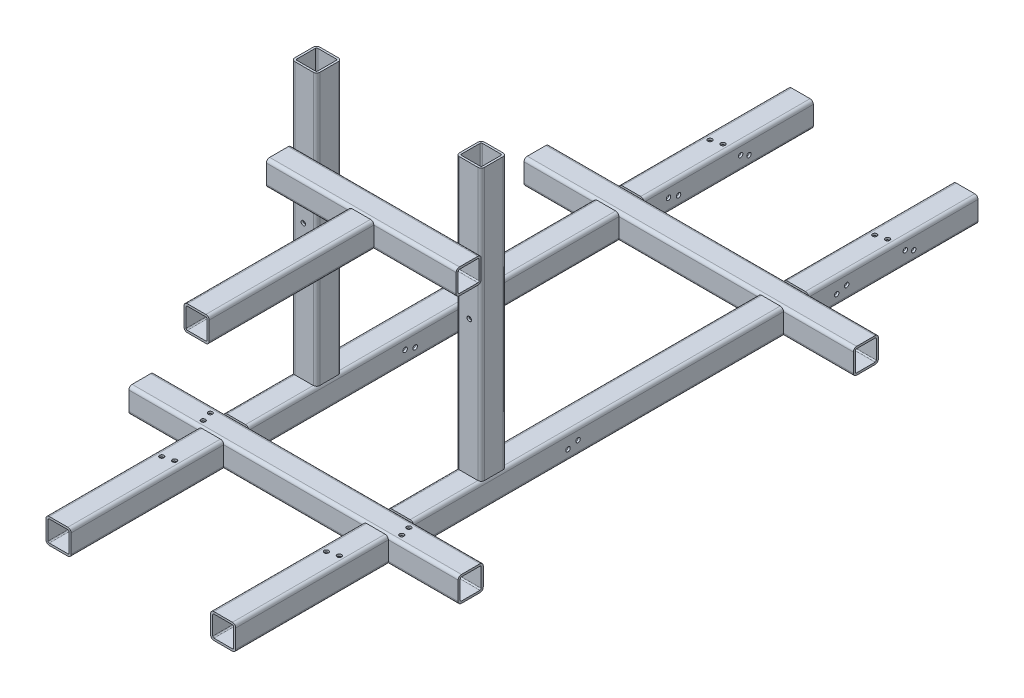
SolidWorks part; units mm, degrees
material "Alumina"
ref_plane "Front Plane" through (0, 0, 0) normal (0, 0, 1) x (1, 0, 0)
ref_plane "Top Plane" through (0, 0, 0) normal (0, 1, 0) x (1, 0, 0)
ref_plane "Right Plane" through (0, 0, 0) normal (1, 0, 0) x (0, 0, -1)
ref_plane "Bottom Face" through (0, 0, 0) normal (0, 1, 0) x (1, 0, 0)
ref_plane "Top Face" through (0, 38.1, 0) normal (0, 1, 0) x (1, 0, 0)
ref_plane "Mid Plane" through (0, 19.05, 0) normal (0, 1, 0) x (1, 0, 0)
ref_plane "Front Face" through (0, 0, 500) normal (0, 0, 1) x (1, 0, 0)
ref_plane "Back Face" through (0, 0, -500) normal (0, 0, 1) x (1, 0, 0)
ref_plane "Left Face" through (250, 0, 0) normal (1, 0, 0) x (0, 0, -1)
ref_plane "Right Face" through (-250, 0, 0) normal (1, 0, 0) x (0, 0, -1)
ref_plane "Divider Plane" through (0, 0, 140) normal (0, 0, 1) x (1, 0, 0)
ref_plane "Max Height Plane" through (0, 450, 0) normal (0, 1, 0) x (1, 0, 0)
ref_plane "Electronics Box Plane" through (0, 338.1, 0) normal (0, 1, 0) x (1, 0, 0)
sketch "Sketch2" plane through (250, 0, 0) normal (1, 0, 0) x (0, 0, -1)
  line L0 (330, 38.1) -> (-330, 38.1) construction
  line L5 (330, 0) -> (-330, 0) construction
  line L6 (0, 220) -> (0, -220) construction
  line L7 (-314.05, 38.1) -> (-285.95, 38.1)
  line L8 (-280.95, 33.1) -> (-280.95, 5)
  line L9 (-315.875, 33.1) -> (-315.875, 5)
  line L10 (-314.05, 3.175) -> (-285.95, 3.175)
  line L11 (-285.95, 0) -> (-314.05, 0)
  line L12 (-319.05, 5) -> (-319.05, 33.1)
  line L13 (-300, 38.1) -> (-300, 0) construction
  line L14 (-319.05, 19.05) -> (-280.95, 19.05) construction
  line L15 (-284.125, 5) -> (-284.125, 33.1)
  line L16 (-285.95, 34.925) -> (-314.05, 34.925)
  line L17 (-300, 34.925) -> (-300, 3.175) construction
  line L18 (-315.875, 19.05) -> (-284.125, 19.05) construction
  arc A0 (-285.95, 38.1) -> (-280.95, 33.1) centre (-285.95, 33.1) cw
  arc A1 (-280.95, 5) -> (-285.95, 0) centre (-285.95, 5) cw
  arc A2 (-314.05, 0) -> (-319.05, 5) centre (-314.05, 5) cw
  arc A3 (-319.05, 33.1) -> (-314.05, 38.1) centre (-314.05, 33.1) cw
  arc A4 (-315.875, 5) -> (-314.05, 3.175) centre (-314.05, 5) ccw
  arc A5 (-285.95, 3.175) -> (-284.125, 5) centre (-285.95, 5) ccw
  arc A6 (-284.125, 33.1) -> (-285.95, 34.925) centre (-285.95, 33.1) ccw
  arc A7 (-314.05, 34.925) -> (-315.875, 33.1) centre (-314.05, 33.1) ccw
  point P20 (-300, 19.05)
  point P39 (-300, 19.05)
  dimension "D1" = 5
  dimension "D2" = 300
  dimension "D3" = 3.175
extrude "Front Cross-Car Member" add sketch "Sketch2" against normal up to surface (500 mm away) up to plane "Right Face"
sketch "Sketch5" plane through (250, 0, 0) normal (1, 0, 0) x (0, 0, -1)
  line L0 (285.95, 38.1) -> (314.05, 38.1)
  line L1 (319.05, 33.1) -> (319.05, 5)
  line L2 (314.05, 0) -> (285.95, 0)
  line L3 (280.95, 5) -> (280.95, 33.1)
  line L4 (300, 38.1) -> (300, 0) construction
  line L5 (280.95, 19.05) -> (319.05, 19.05) construction
  line L6 (285.95, 34.925) -> (314.05, 34.925)
  line L7 (315.875, 33.1) -> (315.875, 5)
  line L8 (314.05, 3.175) -> (285.95, 3.175)
  line L9 (284.125, 5) -> (284.125, 33.1)
  line L10 (300, 34.925) -> (300, 3.175) construction
  line L11 (284.125, 19.05) -> (315.875, 19.05) construction
  line L12 (330, 0) -> (-330, 0) construction
  line L14 (330, 38.1) -> (-330, 38.1) construction
  line L15 (0, 220) -> (0, -220) construction
  arc A0 (314.05, 38.1) -> (319.05, 33.1) centre (314.05, 33.1) cw
  arc A1 (319.05, 5) -> (314.05, 0) centre (314.05, 5) cw
  arc A2 (285.95, 0) -> (280.95, 5) centre (285.95, 5) cw
  arc A3 (280.95, 33.1) -> (285.95, 38.1) centre (285.95, 33.1) cw
  arc A4 (314.05, 34.925) -> (315.875, 33.1) centre (314.05, 33.1) cw
  arc A5 (315.875, 5) -> (314.05, 3.175) centre (314.05, 5) cw
  arc A6 (285.95, 3.175) -> (284.125, 5) centre (285.95, 5) cw
  arc A7 (284.125, 33.1) -> (285.95, 34.925) centre (285.95, 33.1) cw
  point P32 (300, 19.05)
  point P33 (300, 19.05)
  dimension "D2" = 5
  dimension "D1" = 3.175
  dimension "D3" = 300
extrude "Back Cross-Car Member" add sketch "Sketch5" against normal up to surface (500 mm away) separate body up to plane "Right Face"
sketch "Sketch6" plane through (0, 0, -500) normal (0, 0, 1) x (1, 0, 0)
  line L0 (110.95, 38.1) -> (139.05, 38.1)
  line L1 (144.05, 33.1) -> (144.05, 5)
  line L2 (109.125, 33.1) -> (109.125, 5)
  line L3 (110.95, 3.175) -> (139.05, 3.175)
  line L4 (139.05, 0) -> (110.95, 0)
  line L5 (105.95, 5) -> (105.95, 33.1)
  line L6 (125, 38.1) -> (125, 0) construction
  line L7 (105.95, 19.05) -> (144.05, 19.05) construction
  line L8 (140.875, 5) -> (140.875, 33.1)
  line L9 (139.05, 34.925) -> (110.95, 34.925)
  line L10 (125, 34.925) -> (125, 3.175) construction
  line L11 (109.125, 19.05) -> (140.875, 19.05) construction
  line L12 (330, 38.1) -> (-330, 38.1) construction
  line L13 (330, 0) -> (-330, 0) construction
  line L14 (0, -220) -> (0, 220) construction
  arc A0 (139.05, 38.1) -> (144.05, 33.1) centre (139.05, 33.1) cw
  arc A1 (144.05, 5) -> (139.05, 0) centre (139.05, 5) cw
  arc A2 (110.95, 0) -> (105.95, 5) centre (110.95, 5) cw
  arc A3 (105.95, 33.1) -> (110.95, 38.1) centre (110.95, 33.1) cw
  arc A4 (109.125, 5) -> (110.95, 3.175) centre (110.95, 5) ccw
  arc A5 (139.05, 3.175) -> (140.875, 5) centre (139.05, 5) ccw
  arc A6 (140.875, 33.1) -> (139.05, 34.925) centre (139.05, 33.1) ccw
  arc A7 (110.95, 34.925) -> (109.125, 33.1) centre (110.95, 33.1) ccw
  point P16 (125, 19.05)
  point P33 (125, 19.05)
  dimension "D1" = 5
  dimension "D2" = 3.175
  dimension "D3" = 125
extrude "Back Left Along-Car Member" add sketch "Sketch6" along normal blind 180.95 and the other way blind 76.2
extrude "Middle Left Along-Car Member" add sketch "Sketch6<2>" along normal blind 561.9 from offset 219.05
sketch "Sketch6<2>" plane through (0, 0, -500) normal (0, 0, 1) x (1, 0, 0) same geometry as "Sketch6"
extrude "Front Left Along-Car Member" add sketch "Sketch6<3>" along normal blind 231.75 from offset 819.05
sketch "Sketch6<3>" plane through (0, 0, -500) normal (0, 0, 1) x (1, 0, 0) same geometry as "Sketch6"
sketch "Sketch7" plane through (0, 0, -500) normal (0, 0, 1) x (1, 0, 0)
  line L0 (-139.05, 38.1) -> (-110.95, 38.1)
  line L1 (-105.95, 33.1) -> (-105.95, 5)
  line L2 (-140.875, 33.1) -> (-140.875, 5)
  line L3 (-139.05, 3.175) -> (-110.95, 3.175)
  line L4 (-110.95, 0) -> (-139.05, 0)
  line L5 (-144.05, 5) -> (-144.05, 33.1)
  line L6 (-125, 38.1) -> (-125, 0) construction
  line L7 (-144.05, 19.05) -> (-105.95, 19.05) construction
  line L8 (-109.125, 5) -> (-109.125, 33.1)
  line L9 (-110.95, 34.925) -> (-139.05, 34.925)
  line L10 (-125, 34.925) -> (-125, 3.175) construction
  line L11 (-140.875, 19.05) -> (-109.125, 19.05) construction
  line L12 (330, 38.1) -> (-330, 38.1) construction
  line L13 (330, 0) -> (-330, 0) construction
  line L14 (0, -220) -> (0, 220) construction
  arc A0 (-110.95, 38.1) -> (-105.95, 33.1) centre (-110.95, 33.1) cw
  arc A1 (-105.95, 5) -> (-110.95, 0) centre (-110.95, 5) cw
  arc A2 (-139.05, 0) -> (-144.05, 5) centre (-139.05, 5) cw
  arc A3 (-144.05, 33.1) -> (-139.05, 38.1) centre (-139.05, 33.1) cw
  arc A4 (-140.875, 5) -> (-139.05, 3.175) centre (-139.05, 5) ccw
  arc A5 (-110.95, 3.175) -> (-109.125, 5) centre (-110.95, 5) ccw
  arc A6 (-109.125, 33.1) -> (-110.95, 34.925) centre (-110.95, 33.1) ccw
  arc A7 (-139.05, 34.925) -> (-140.875, 33.1) centre (-139.05, 33.1) ccw
  point P16 (-125, 19.05)
  point P33 (-125, 19.05)
  dimension "D1" = 5
  dimension "D2" = 3.175
  dimension "D3" = 125
extrude "Back Right Along-Car Member" add sketch "Sketch7" along normal blind 180.95 and the other way blind 76.2
extrude "Middle Right Along-Car Member" add sketch "Sketch7<2>" along normal blind 561.9 from offset 219.05
sketch "Sketch7<2>" plane through (0, 0, -500) normal (0, 0, 1) x (1, 0, 0) same geometry as "Sketch7"
extrude "Front Right Along-Car Member" add sketch "Sketch7<3>" along normal blind 231.75 from offset 819.05
sketch "Sketch7<3>" plane through (0, 0, -500) normal (0, 0, 1) x (1, 0, 0) same geometry as "Sketch7"
sketch "Sketch8" plane through (0, 38.1, 0) normal (0, 1, 0) x (1, 0, 0)
  line L0 (-139.05, -140) -> (-110.95, -140)
  line L1 (-105.95, -145) -> (-105.95, -173.1)
  line L2 (-140.875, -145) -> (-140.875, -173.1)
  line L3 (-139.05, -174.925) -> (-110.95, -174.925)
  line L4 (-110.95, -178.1) -> (-139.05, -178.1)
  line L5 (-144.05, -173.1) -> (-144.05, -145)
  line L6 (-125, -140) -> (-125, -178.1) construction
  line L7 (-144.05, -159.05) -> (-105.95, -159.05) construction
  line L8 (-109.125, -173.1) -> (-109.125, -145)
  line L9 (-110.95, -143.175) -> (-139.05, -143.175)
  line L10 (-125, -143.175) -> (-125, -174.925) construction
  line L11 (-140.875, -159.05) -> (-109.125, -159.05) construction
  line L12 (-220, -140) -> (220, -140) construction
  line L13 (0, -247.5) -> (0, 247.5) construction
  arc A0 (-110.95, -140) -> (-105.95, -145) centre (-110.95, -145) cw
  arc A1 (-105.95, -173.1) -> (-110.95, -178.1) centre (-110.95, -173.1) cw
  arc A2 (-139.05, -178.1) -> (-144.05, -173.1) centre (-139.05, -173.1) cw
  arc A3 (-144.05, -145) -> (-139.05, -140) centre (-139.05, -145) cw
  arc A4 (-140.875, -173.1) -> (-139.05, -174.925) centre (-139.05, -173.1) ccw
  arc A5 (-110.95, -174.925) -> (-109.125, -173.1) centre (-110.95, -173.1) ccw
  arc A6 (-109.125, -145) -> (-110.95, -143.175) centre (-110.95, -145) ccw
  arc A7 (-139.05, -143.175) -> (-140.875, -145) centre (-139.05, -145) ccw
  point P16 (-125, -159.05)
  point P33 (-125, -159.05)
  dimension "D1" = 5
  dimension "D2" = 3.175
  dimension "D3" = 38.1
  dimension "D4" = 125
extrude "Right Vertical Member" add sketch "Sketch8" along normal up to surface (411.9 mm away) up to plane "Max Height Plane"
sketch "Sketch10" plane through (0, 38.1, 0) normal (0, 1, 0) x (1, 0, 0)
  line L0 (110.95, -140) -> (139.05, -140)
  line L1 (144.05, -145) -> (144.05, -173.1)
  line L2 (109.125, -145) -> (109.125, -173.1)
  line L3 (110.95, -174.925) -> (139.05, -174.925)
  line L4 (139.05, -178.1) -> (110.95, -178.1)
  line L5 (105.95, -173.1) -> (105.95, -145)
  line L6 (125, -140) -> (125, -178.1) construction
  line L7 (105.95, -159.05) -> (144.05, -159.05) construction
  line L8 (140.875, -173.1) -> (140.875, -145)
  line L9 (139.05, -143.175) -> (110.95, -143.175)
  line L10 (125, -143.175) -> (125, -174.925) construction
  line L11 (109.125, -159.05) -> (140.875, -159.05) construction
  line L12 (-220, -140) -> (220, -140) construction
  line L13 (0, -247.5) -> (0, 247.5) construction
  arc A0 (139.05, -140) -> (144.05, -145) centre (139.05, -145) cw
  arc A1 (144.05, -173.1) -> (139.05, -178.1) centre (139.05, -173.1) cw
  arc A2 (110.95, -178.1) -> (105.95, -173.1) centre (110.95, -173.1) cw
  arc A3 (105.95, -145) -> (110.95, -140) centre (110.95, -145) cw
  arc A4 (109.125, -173.1) -> (110.95, -174.925) centre (110.95, -173.1) ccw
  arc A5 (139.05, -174.925) -> (140.875, -173.1) centre (139.05, -173.1) ccw
  arc A6 (140.875, -145) -> (139.05, -143.175) centre (139.05, -145) ccw
  arc A7 (110.95, -143.175) -> (109.125, -145) centre (110.95, -145) ccw
  point P16 (125, -159.05)
  point P33 (125, -159.05)
  dimension "D1" = 5
  dimension "D2" = 3.175
  dimension "D3" = 38.1
  dimension "D4" = 125
extrude "Left Vertical Member" add sketch "Sketch10" along normal up to surface (411.9 mm away) up to plane "Max Height Plane"
sketch "Sketch11" plane through (250, 0, 0) normal (1, 0, 0) x (0, 0, -1)
  line L0 (-211.2, 338.1) -> (-183.1, 338.1)
  line L1 (-178.1, 333.1) -> (-178.1, 305)
  line L2 (-213.025, 333.1) -> (-213.025, 305)
  line L3 (-211.2, 303.175) -> (-183.1, 303.175)
  line L4 (-183.1, 300) -> (-211.2, 300)
  line L5 (-216.2, 305) -> (-216.2, 333.1)
  line L6 (-197.15, 338.1) -> (-197.15, 300) construction
  line L7 (-216.2, 319.05) -> (-178.1, 319.05) construction
  line L8 (-181.275, 305) -> (-181.275, 333.1)
  line L9 (-183.1, 334.925) -> (-211.2, 334.925)
  line L10 (-197.15, 334.925) -> (-197.15, 303.175) construction
  line L11 (-213.025, 319.05) -> (-181.275, 319.05) construction
  line L12 (-140, 220) -> (-140, -220) construction
  line L13 (330, 338.1) -> (-330, 338.1) construction
  arc A0 (-183.1, 338.1) -> (-178.1, 333.1) centre (-183.1, 333.1) cw
  arc A1 (-178.1, 305) -> (-183.1, 300) centre (-183.1, 305) cw
  arc A2 (-211.2, 300) -> (-216.2, 305) centre (-211.2, 305) cw
  arc A3 (-216.2, 333.1) -> (-211.2, 338.1) centre (-211.2, 333.1) cw
  arc A4 (-213.025, 305) -> (-211.2, 303.175) centre (-211.2, 305) ccw
  arc A5 (-183.1, 303.175) -> (-181.275, 305) centre (-183.1, 305) ccw
  arc A6 (-181.275, 333.1) -> (-183.1, 334.925) centre (-183.1, 333.1) ccw
  arc A7 (-211.2, 334.925) -> (-213.025, 333.1) centre (-211.2, 333.1) ccw
  point P16 (-197.15, 319.05)
  point P33 (-197.15, 319.05)
  dimension "D1" = 5
  dimension "D2" = 3.175
  dimension "D3" = 38.1
  dimension "D4" = 38.1
extrude "Upper Cross-Car Member" add sketch "Sketch11" against normal blind 288.1 from offset 105.95 offset against normal yes
sketch "Sketch12" plane through (0, 0, 140) normal (0, 0, 1) x (1, 0, 0)
  line L0 (-14.05, 338.1) -> (14.05, 338.1)
  line L1 (19.05, 333.1) -> (19.05, 305)
  line L2 (-15.875, 333.1) -> (-15.875, 305)
  line L3 (-14.05, 303.175) -> (14.05, 303.175)
  line L4 (14.05, 300) -> (-14.05, 300)
  line L5 (-19.05, 305) -> (-19.05, 333.1)
  line L6 (0, 338.1) -> (0, 300) construction
  line L7 (-19.05, 319.05) -> (19.05, 319.05) construction
  line L8 (15.875, 305) -> (15.875, 333.1)
  line L9 (14.05, 334.925) -> (-14.05, 334.925)
  line L10 (0, 334.925) -> (0, 303.175) construction
  line L11 (-15.875, 319.05) -> (15.875, 319.05) construction
  line L12 (330, 338.1) -> (-330, 338.1) construction
  line L13 (0, -247.5) -> (0, 247.5) construction
  arc A0 (14.05, 338.1) -> (19.05, 333.1) centre (14.05, 333.1) cw
  arc A1 (19.05, 305) -> (14.05, 300) centre (14.05, 305) cw
  arc A2 (-14.05, 300) -> (-19.05, 305) centre (-14.05, 305) cw
  arc A3 (-19.05, 333.1) -> (-14.05, 338.1) centre (-14.05, 333.1) cw
  arc A4 (-15.875, 305) -> (-14.05, 303.175) centre (-14.05, 305) ccw
  arc A5 (14.05, 303.175) -> (15.875, 305) centre (14.05, 305) ccw
  arc A6 (15.875, 333.1) -> (14.05, 334.925) centre (14.05, 333.1) ccw
  arc A7 (-14.05, 334.925) -> (-15.875, 333.1) centre (-14.05, 333.1) ccw
  point P16 (0, 319.05)
  point P33 (0, 319.05)
  dimension "D1" = 5
  dimension "D2" = 3.175
  dimension "D3" = 38.1
extrude "E-Box Platform Base" add sketch "Sketch12" along normal blind 250 from offset 76.2
sketch "Sketch13" plane through (0, 0, 140) normal (0, 0, -1) x (-1, 0, 0)
  circle A2 centre (126.05, 244.1) radius 3.3782
  circle A3 centre (-125.95, 244.1) radius 3.3782
extrude "Cut-Extrude1" cut sketch "Sketch13" against normal up to surface (38.1 mm away) up to face at (125, 171.55, 178.1)
sketch "Sketch14" plane through (0, 38.1, 0) normal (0, 1, 0) x (1, 0, 0)
  circle A0 centre (-132.62, -386.5) radius 3.3782
  circle A1 centre (-117.38, -382.1) radius 3.3782
  circle A2 centre (-152.9, -292.38) radius 3.3782
  circle A3 centre (-148.5, -307.62) radius 3.3782
  circle A8 centre (152.9, -307.62) radius 3.3782
  circle A9 centre (148.5, -292.38) radius 3.3782
  circle A10 centre (117.38, -386.5) radius 3.3782
  circle A11 centre (132.62, -382.1) radius 3.3782
extrude "Cut-Extrude2" cut sketch "Sketch14" against normal up to surface (38.1 mm away) up to face at (125, 0, 434.925)
sketch "Sketch16" plane through (105.95, 0, 0) normal (-1, 0, 0) x (0, 0, 1)
  circle A0 centre (-478.5, 15.24) radius 3.3782
  circle A1 centre (-465.8, 21.59) radius 3.3782
extrude "Cut-Extrude4" cut sketch "Sketch16" along normal up to surface and the other way up to surface up to face at (-144.05, 19.05, -447.625) other way up to face at (144.05, 19.05, -447.625)
sketch "Sketch17" plane through (-144.05, 0, 0) normal (-1, 0, 0) x (0, 0, 1)
  circle A1 centre (43.5864, 20.25) radius 3.3782
  circle A2 centre (28.3464, 15.85) radius 3.3782
  circle A3 centre (-356.2832, 20.25) radius 3.3782
  circle A4 centre (-371.5232, 15.85) radius 3.3782
sketch "Sketch18" plane through (0, 38.1, 0) normal (0, 1, 0) x (1, 0, 0)
  circle A0 centre (-132.62, 446) radius 3.3782
  circle A1 centre (-117.38, 450.4) radius 3.3782
  circle A2 centre (117.38, 446) radius 3.3782
  circle A3 centre (132.62, 450.4) radius 3.3782
sketch "Sketch19" plane through (144.05, 0, 0) normal (1, 0, 0) x (0, 0, -1)
  circle A0 centre (-46.3207, 15.85) radius 3.3782
  circle A1 centre (-31.0807, 20.25) radius 3.3782
  circle A2 centre (376.8433, 20.25) radius 3.3782
  circle A3 centre (361.6033, 15.85) radius 3.3782
extrude "Cut-Extrude5" cut sketch "Sketch17" against normal up to surface (38.1 mm away) up to face at (-105.95, 19.05, 0)
extrude "Cut-Extrude6" cut sketch "Sketch18" against normal up to surface (38.1 mm away) up to face at (-125, 0, -447.625)
extrude "Cut-Extrude7" cut sketch "Sketch19" against normal up to surface (38.1 mm away) up to face at (105.95, 19.05, 0)
equation "\"D1@Front Face\" = \"frameLength@Master Assembly.SLDASM\" / 2"
equation "\"D1@Back Face\" = \"frameLength@Master Assembly.SLDASM\" / 2"
equation "\"D1@Left Face\"=\"frameWidth@Master Assembly.SLDASM\"/2"
equation "\"D1@Right Face\" = \"frameWidth@Master Assembly.SLDASM\" / 2"
equation "\"D1@Top Face\"=\"frameTubeStockHeight@Master Assembly.SLDASM\""
equation "\"D2@Sketch2\"=\"frameMemberDistLength@Master Assembly.SLDASM\"/2"
equation "\"D3@Sketch2\"=\"frameTubeStockWallThickness@Master Assembly.SLDASM\""
equation "\"D1@Sketch5\"=\"frameTubeStockWallThickness@Master Assembly.SLDASM\""
equation "\"D3@Sketch5\"=\"frameMemberDistLength@Master Assembly.SLDASM\"/2"
equation "\"D3@Sketch6\"=\"frameMemberDistWidth@Master Assembly.SLDASM\"/2"
equation "\"D1@Back Left Along-Car Member\"=( \"frameLength@Master Assembly.Assembly\" - \"frameMemberDistLength@Master Assembly.Assembly\" - \"frameTubeStockHeight@Master Assembly.Assembly\" )  / 2"
equation "\"D19@Middle Left Along-Car Member\" = ( \"frameLength@Master Assembly.SLDASM\" - \"frameMemberDistLength@Master Assembly.SLDASM\" + \"frameTubeStockHeight@Master Assembly.SLDASM\" ) / 2"
equation "\"D1@Middle Left Along-Car Member\"=\"frameMemberDistLength@Master Assembly.SLDASM\" - \"frameTubeStockHeight@Master Assembly.SLDASM\""
equation "\"D19@Front Left Along-Car Member\"=( \"frameLength@Master Assembly.SLDASM\" - \"frameMemberDistLength@Master Assembly.SLDASM\" )  / 2 + \"frameMemberDistLength@Master Assembly.SLDASM\" + \"frameTubeStockHeight@Master Assembly.SLDASM\" / 2"
equation "\"D1@Front Left Along-Car Member\" =  ( \"frameLength@Master Assembly.Assembly\" - \"frameMemberDistLength@Master Assembly.Assembly\" - \"frameTubeStockHeight@Master Assembly.Assembly\" )  / 2 + 2in"
equation "\"D3@Sketch7\"=\"frameMemberDistWidth@Master Assembly.SLDASM\"/2"
equation "\"D1@Back Right Along-Car Member\"=(\"frameLength@Master Assembly.SLDASM\" - \"frameMemberDistLength@Master Assembly.SLDASM\" - \"frameTubeStockHeight@Master Assembly.SLDASM\")  / 2"
equation "\"D19@Middle Right Along-Car Member\" = ( \"frameLength@Master Assembly.SLDASM\" - \"frameMemberDistLength@Master Assembly.SLDASM\" + \"frameTubeStockHeight@Master Assembly.SLDASM\" ) / 2"
equation "\"D1@Middle Right Along-Car Member\"=\"frameMemberDistLength@Master Assembly.SLDASM\" - \"frameTubeStockHeight@Master Assembly.SLDASM\""
equation "\"D19@Front Right Along-Car Member\"=( \"frameLength@Master Assembly.SLDASM\" - \"frameMemberDistLength@Master Assembly.SLDASM\" )  / 2 + \"frameMemberDistLength@Master Assembly.SLDASM\" + \"frameTubeStockHeight@Master Assembly.SLDASM\" / 2"
equation "\"D1@Front Right Along-Car Member\"=( \"frameLength@Master Assembly.Assembly\" - \"frameMemberDistLength@Master Assembly.Assembly\" - \"frameTubeStockHeight@Master Assembly.Assembly\" )  / 2 + 2in"
equation "\"D1@Divider Plane\"= \"frameDividerPlaneOffset@Master Assembly.SLDASM\""
equation "\"D3@Sketch8\"=\"frameTubeStockHeight@Master Assembly.SLDASM\""
equation "\"D4@Sketch8\"=\"frameMemberDistWidth@Master Assembly.SLDASM\"/2"
equation "\"D1@Max Height Plane\" = \"frameHeight@Master Assembly.SLDASM\""
equation "\"D4@Sketch10\"=\"frameMemberDistWidth@Master Assembly.SLDASM\"/2"
equation "\"D1@Electronics Box Plane\" = \"eboxPlaneHeight@Master Assembly.SLDASM\""
equation "\"D4@Sketch11\"=\"frameTubeStockHeight@Master Assembly.SLDASM\""
equation "\"D19@Upper Cross-Car Member\" = ( \"frameWidth@Master Assembly.SLDASM\" - \"frameMemberDistWidth@Master Assembly.SLDASM\" - \"frameTubeStockHeight@Master Assembly.SLDASM\" ) / 2"
equation "\"D1@Upper Cross-Car Member\" = \"frameMemberDistWidth@Master Assembly.SLDASM\" + \"frameTubeStockHeight@Master Assembly.SLDASM\""
equation "\"D19@E-Box Platform Base\"= \"frameTubeStockHeight@Master Assembly.SLDASM\" * 2"
equation "\"D2@Sketch6\"=\"frameTubeStockWallThickness@Master Assembly.SLDASM\""
equation "\"D2@Sketch7\"=\"frameTubeStockWallThickness@Master Assembly.SLDASM\""
equation "\"D2@Sketch8\"=\"frameTubeStockWallThickness@Master Assembly.SLDASM\""
equation "\"D3@Sketch10\"=\"frameTubeStockHeight@Master Assembly.SLDASM\""
equation "\"D2@Sketch10\"=\"frameTubeStockWallThickness@Master Assembly.SLDASM\""
equation "\"D3@Sketch11\"=\"frameTubeStockHeight@Master Assembly.SLDASM\""
equation "\"D2@Sketch11\"=\"frameTubeStockWallThickness@Master Assembly.SLDASM\""
equation "\"D3@Sketch12\"=\"frameTubeStockHeight@Master Assembly.SLDASM\""
equation "\"D2@Sketch12\"=\"frameTubeStockWallThickness@Master Assembly.SLDASM\""
